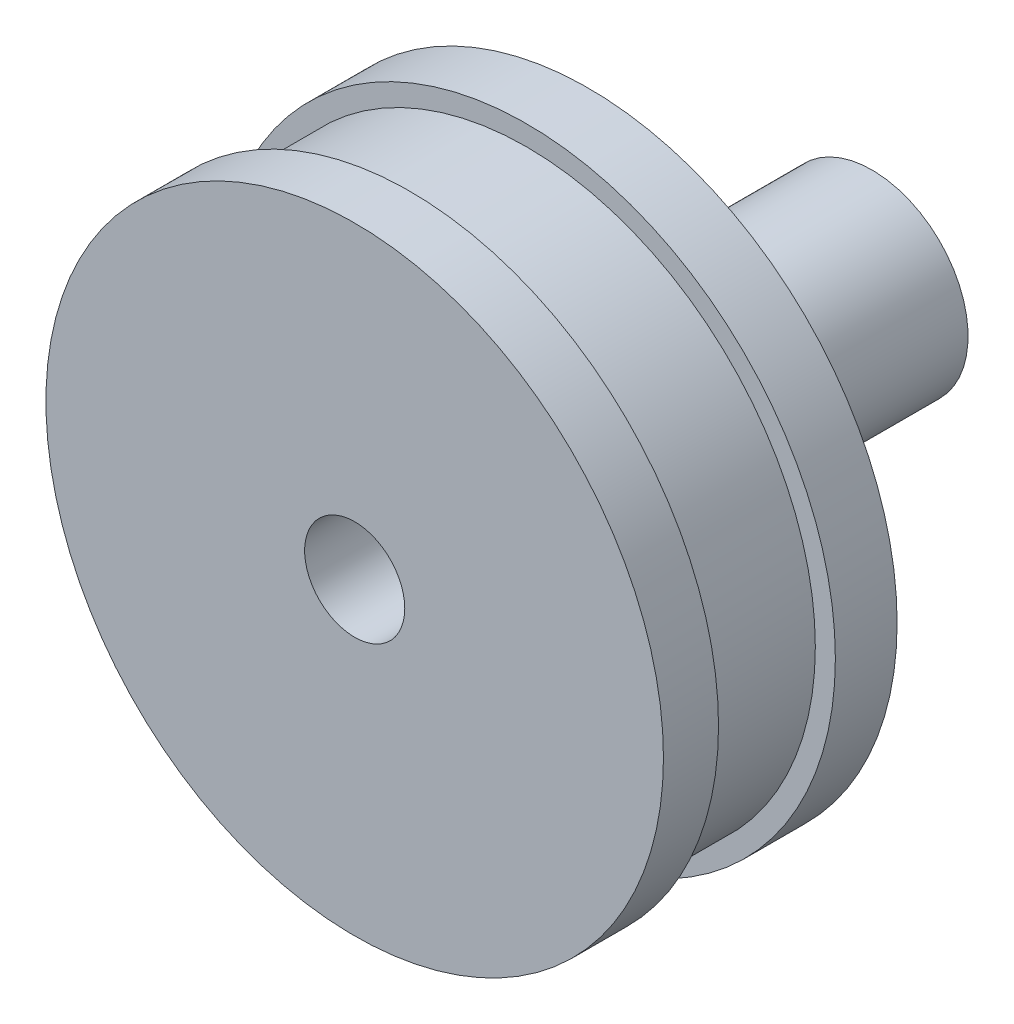
SolidWorks part; units mm, degrees
ref_plane "前视基准面" through (0, 0, 0) normal (0, 0, 1) x (1, 0, 0)
ref_plane "上视基准面" through (0, 0, 0) normal (0, 1, 0) x (1, 0, 0)
ref_plane "右视基准面" through (0, 0, 0) normal (1, 0, 0) x (0, 0, -1)
sketch "草图1" plane through (0, 0, 0) normal (0, 0, 1) x (1, 0, 0)
  circle A0 centre (0, 0) radius 18.5
  circle A2 centre (0, 0) radius 3
extrude "凸台-拉伸1" add sketch "草图1" along normal blind 14
ref_plane "基准面4" through (0, 0, 7.7) normal (0, 0, 1) x (1, 0, 0)
sketch "草图2" plane through (0, 0, 7.7) normal (0, 0, 1) x (1, 0, 0)
  circle A0 centre (0, 0) radius 17.3
  circle A1 centre (0, 0) radius 18.5
extrude "切除-拉伸1" cut sketch "草图2" against normal blind 2.2
extrude "切除-拉伸2" cut sketch "草图2<2>" along normal blind 0.8
sketch "草图2<2>" plane through (0, 0, 7.7) normal (0, 0, 1) x (1, 0, 0) same geometry as "草图2"
extrude "切除-拉伸3" cut sketch "草图2<4>" against normal blind 4
sketch "草图2<4>" plane through (0, 0, 7.7) normal (0, 0, 1) x (1, 0, 0) same geometry as "草图2"
extrude "切除-拉伸5" cut sketch "草图2<6>" along normal blind 3
sketch "草图2<6>" plane through (0, 0, 7.7) normal (0, 0, 1) x (1, 0, 0) same geometry as "草图2"
sketch "草图3" plane through (0, 0, 0) normal (0, 0, -1) x (-1, 0, 0)
  circle A0 centre (0, 0) radius 7
extrude "凸台-拉伸3" add sketch "草图3" along normal blind 5
sketch "草图4" plane through (0, 0, -5) normal (0, 0, -1) x (-1, 0, 0)
  circle A0 centre (0, 0) radius 5.75
  dimension "D1" = 11.5
extrude "凸台-拉伸4" add sketch "草图4" along normal blind 12
